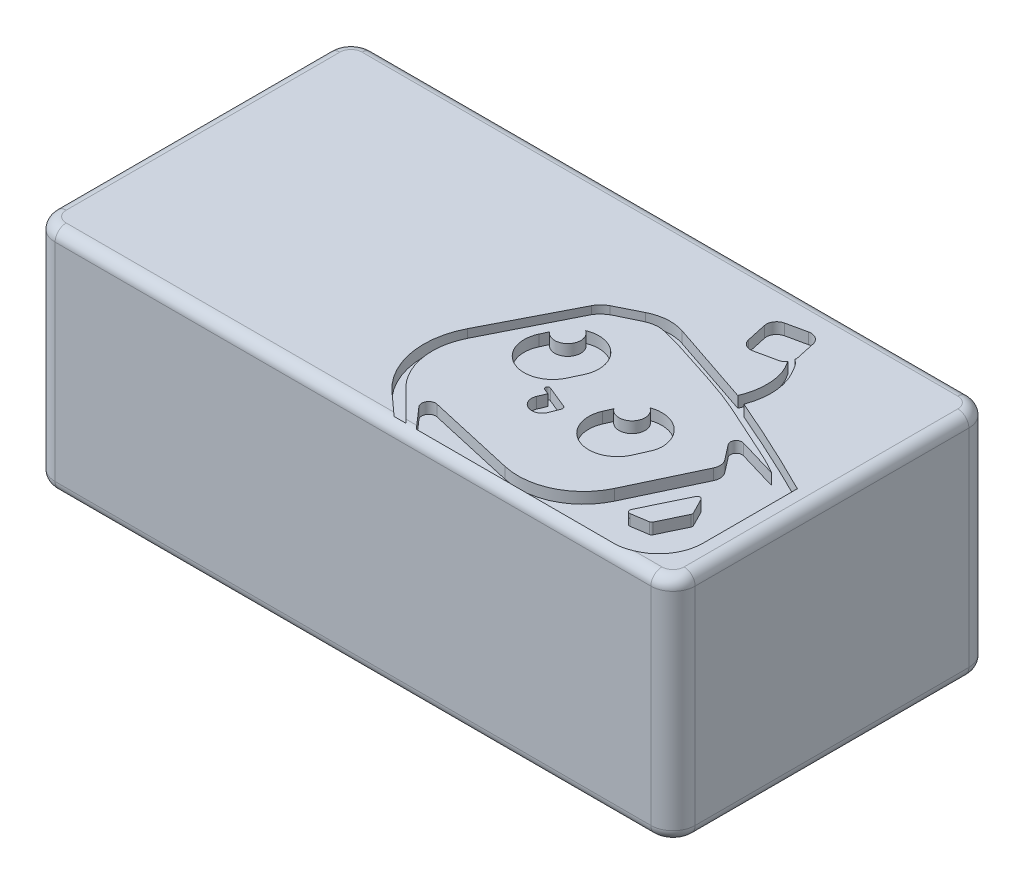
SolidWorks part; units mm, degrees
ref_plane "Front Plane" through (0, 0, 0) normal (0, 0, 1) x (1, 0, 0)
ref_plane "Top Plane" through (0, 0, 0) normal (0, 1, 0) x (1, 0, 0)
ref_plane "Right Plane" through (0, 0, 0) normal (1, 0, 0) x (0, 0, -1)
sketch "Sketch1" plane through (0, 0, 0) normal (0, 1, 0) x (1, 0, 0)
  line L1 (-12.5, -7.5) -> (12.5, -7.5)
  line L2 (-12.5, -7.5) -> (-12.5, 7.5)
  line L3 (-12.5, 7.5) -> (12.5, 7.5)
  line L4 (12.5, -7.5) -> (12.5, 7.5)
  line L5 (-12.5, -7.5) -> (12.5, 7.5) construction
  line L6 (-12.5, 7.5) -> (12.5, -7.5) construction
  point P0 (0, 0)
  dimension "D1" = 15
  dimension "D2" = 25
extrude "Boss-Extrude1" add sketch "Sketch1" along normal mid plane 10.3636
sketch "Sketch2"
  line L0 (180.6347, 501.4527) -> (923.3014, 501.4527) construction
  line L1 (-4.3636, -6.8247) -> (-5.4332, -6.8247)
  line L2 (-7.4332, -4.8247) -> (-7.4332, 4.9107)
  line L3 (-5.4332, 6.9107) -> (5.5194, 6.9107)
  line L4 (7.5194, 4.9107) -> (7.5194, -0.5662)
  line L5 (-4.3636, -6.8247) -> (-5.4332, -5.9231)
  line L6 (-6.1924, -1.7529) -> (-4.2938, 1.9428)
  line L7 (-3.865, 2.3672) -> (-2.7996, 2.901)
  line L8 (-1.2582, 3.0091) -> (2.5252, 1.7368)
  line L9 (1.1191, 3.8213) -> (2.0886, 4.0312)
  line L10 (0.3914, 5.0703) -> (0.5877, 4.1635)
  line L11 (0.7505, 5.6278) -> (1.6384, 5.82)
  line L12 (2.2124, 5.4502) -> (2.4063, 4.5547)
  line L13 (-3.9786, 1.516) -> (-5.8093, -2.1281)
  line L14 (-5.0214, -5.6732) -> (-3.5615, -6.8247)
  line L15 (-3.5615, -6.8247) -> (-3.4302, -6.8247)
  line L16 (-3.4302, -6.8247) -> (-4.2328, -5.907)
  line L17 (-3.9274, -5.3946) -> (0.0559, -6.2971)
  line L18 (3.3761, -4.6797) -> (4.8095, -1.6459)
  line L19 (4.7467, -1.0692) -> (4.2301, -0.4014)
  line L20 (4.5099, 0.0079) -> (6.3202, -0.5264)
  line L21 (5.5264, -3.1622) -> (4.5784, -5.1306)
  line L22 (4.7155, -5.3155) -> (5.4654, -5.1989)
  line L23 (5.5626, -5.1268) -> (6.1187, -3.972)
  line L24 (6.1172, -3.8562) -> (5.7591, -3.1592)
  line L25 (-2.0003, -2.2019) -> (-0.9974, -2.6112)
  line L26 (-2.0746, -2.3822) -> (-1.8339, -2.4825)
  line L27 (-1.8339, -2.4825) -> (-1.9832, -2.8408)
  line L28 (-0.9235, -2.7831) -> (-1.0866, -3.2021)
  line L29 (-4.2134, -0.0245) -> (-4.3655, -0.3473)
  line L30 (-2.0207, -1.4527) -> (-1.7541, -0.8872)
  line L31 (0.2433, -1.578) -> (0.0896, -1.9282)
  line L32 (2.4749, -2.9752) -> (2.7387, -2.3743)
  arc A0 (-5.4332, -6.8247) -> (-7.4332, -4.8247) centre (-5.4332, -4.8247) cw
  arc A1 (5.5194, 6.9107) -> (7.5194, 4.9107) centre (5.5194, 4.9107) cw
  arc A2 (-7.4332, 4.9107) -> (-5.4332, 6.9107) centre (-5.4332, 4.9107) cw
  arc A3 (-5.4332, -5.9231) -> (-6.1924, -1.7529) centre (-3.0963, -3.3434) cw
  arc A4 (-4.2938, 1.9428) -> (-3.865, 2.3672) centre (-3.4302, 1.4991) cw
  arc A5 (-2.7996, 2.901) -> (-1.2582, 3.0091) centre (-1.899, 1.1034) cw
  arc A6 (2.3243, 4.1968) -> (2.0886, 4.0312) centre (2.0103, 4.3931) cw
  arc A7 (1.1191, 3.8213) -> (0.5877, 4.1635) centre (1.0245, 4.2581) cw
  arc A8 (0.3914, 5.0703) -> (0.7505, 5.6278) centre (0.8497, 5.1695) cw
  arc A9 (1.6384, 5.82) -> (2.2124, 5.4502) centre (1.7405, 5.3481) cw
  arc A10 (2.4063, 4.5547) -> (2.4018, 4.4364) centre (2.1731, 4.5042) cw
  arc A11 (3.0047, 1.5345) -> (7.5194, -0.5662) centre (-27.5, -69.926) cw
  arc A12 (-5.0214, -5.6732) -> (-5.8093, -2.1281) centre (-3.2423, -3.4177) cw
  arc A13 (-4.2328, -5.907) -> (-3.9274, -5.3946) centre (-3.9967, -5.7005) cw
  arc A14 (0.0559, -6.2971) -> (3.3761, -4.6797) centre (0.7079, -3.419) ccw
  arc A15 (4.8095, -1.6459) -> (4.7467, -1.0692) centre (4.3077, -1.4088) ccw
  arc A16 (4.2301, -0.4014) -> (4.5099, 0.0079) centre (4.4362, -0.242) cw
  arc A17 (6.1187, -3.972) -> (6.1172, -3.8562) centre (6.0016, -3.9156) ccw
  arc A18 (5.4654, -5.1989) -> (5.5626, -5.1268) centre (5.4454, -5.0704) ccw
  arc A19 (4.5784, -5.1306) -> (4.7155, -5.3155) centre (4.6955, -5.187) ccw
  arc A20 (5.5264, -3.1622) -> (5.7591, -3.1592) centre (5.6435, -3.2186) cw
  arc A21 (-1.9832, -2.8408) -> (-1.0866, -3.2021) centre (-1.537, -3.0267) ccw
  arc A22 (-0.9235, -2.7831) -> (-0.9974, -2.6112) centre (-1.0477, -2.7347) ccw
  arc A23 (-2.0746, -2.3822) -> (-2.0003, -2.2019) centre (-2.0371, -2.2922) cw
  arc A24 (-3.4462, 0.8385) -> (-4.2134, -0.0245) centre (-3.7545, 0.34) cw
  arc A25 (0.2433, -1.578) -> (1.0245, -0.7262) centre (0.7154, -1.2268) ccw
  arc A26 (-3.4462, 0.8385) -> (-1.7259, -0.8201) centre (-2.9478, -0.3661) cw
  arc A27 (1.0245, -0.7262) -> (2.8215, -1.895) centre (1.4807, -1.9907) cw
  arc A28 (-4.3655, -0.3473) -> (-2.0207, -1.4527) centre (-3.1931, -0.9) ccw
  arc A29 (0.0896, -1.9282) -> (2.4749, -2.9752) centre (1.2822, -2.4517) ccw
  arc A30 (-1.7541, -0.8872) -> (-1.7259, -0.8201) centre (-2.5312, -0.5209) ccw
  arc A31 (2.7387, -2.3743) -> (2.8215, -1.895) centre (1.8111, -1.9672) ccw
  spline S0 degree 3 poles (2.5252, 1.7368) (2.6753, 2.0764) (2.7891, 2.6715) (2.6979, 3.5369) (2.4712, 3.981) (2.3243, 4.1968) knots 0 0 0 0 0.430816 0.694599 1 1 1 1
  spline S1 degree 3 poles (2.4018, 4.4364) (2.5923, 4.3118) (2.8046, 3.9742) (3.0654, 3.4498) (3.2578, 2.6374) (3.1673, 1.9694) (3.0047, 1.5345) knots 0 0 0 0 0.211654 0.375148 0.558685 1 1 1 1
  spline S2 degree 3 poles (6.3202, -0.5264) (5.5759, -0.0876) (4.2529, 0.4376) (2.464, 1.3139) (0.9774, 1.7954) (-0.3683, 2.2397) (-1.2804, 2.511) (-1.9161, 2.6531) (-2.3007, 2.5921) (-2.6787, 2.431) (-3.0836, 2.2029) (-3.5846, 2.0136) (-3.8872, 1.717) (-3.9786, 1.516) knots 0 0 0 0 0.229687 0.378724 0.530054 0.645426 0.756187 0.784394 0.817561 0.857699 0.893541 0.941238 1 1 1 1
  dimension "D1" = 2
  dimension "D2" = 0.13
sketch "Sketch4" plane through (0, 5.1818, 0) normal (0, 1, 0) x (1, 0, 0)
  line L0 (-4.3636, -6.8247) -> (-5.4332, -6.8247) construction
  line L1 (-7.4332, -4.8247) -> (-7.4332, 4.9107) construction
  line L2 (7.5194, 4.9107) -> (7.5194, -0.5662) construction
  line L3 (-5.4332, 6.9107) -> (5.5194, 6.9107) construction
  line L4 (-4.3636, -6.8247) -> (-5.4332, -6.8247)
  line L5 (-7.4332, -4.8247) -> (-7.4332, 4.9107)
  line L6 (7.5194, 4.9107) -> (7.5194, -0.5662)
  line L7 (-5.4332, 6.9107) -> (5.5194, 6.9107)
  line L8 (-4.3636, -6.8247) -> (5.5194, -6.8247)
  line L9 (7.5194, -0.5662) -> (7.5194, -4.8247)
  line L10 (-12.5, -7.5) -> (12.5, -7.5) construction
  line L11 (12.5, -7.5) -> (12.5, 7.5) construction
  line L12 (12.5, 7.5) -> (-12.5, 7.5) construction
  line L13 (-12.5, 7.5) -> (-12.5, -7.5) construction
  line L14 (-12.5, -7.5) -> (12.5, -7.5)
  line L15 (12.5, -7.5) -> (12.5, 7.5)
  line L16 (12.5, 7.5) -> (-12.5, 7.5)
  line L17 (-12.5, 7.5) -> (-12.5, -7.5)
  arc A0 (-7.4332, -4.8247) -> (-5.4332, -6.8247) centre (-5.4332, -4.8247) ccw construction
  arc A1 (7.5194, 4.9107) -> (5.5194, 6.9107) centre (5.5194, 4.9107) ccw construction
  arc A2 (-5.4332, 6.9107) -> (-7.4332, 4.9107) centre (-5.4332, 4.9107) ccw construction
  arc A3 (-7.4332, -4.8247) -> (-5.4332, -6.8247) centre (-5.4332, -4.8247) ccw
  arc A4 (7.5194, 4.9107) -> (5.5194, 6.9107) centre (5.5194, 4.9107) ccw
  arc A5 (-5.4332, 6.9107) -> (-7.4332, 4.9107) centre (-5.4332, 4.9107) ccw
  arc A6 (5.5194, -6.8247) -> (7.5194, -4.8247) centre (5.5194, -4.8247) ccw
  dimension "D1" = 2
extrude "Cut-Extrude3" cut sketch "Sketch4" against normal through all
sketch "Sketch5" plane through (0, 5.1818, 0) normal (0, 1, 0) x (1, 0, 0)
  line L0 (-3.9274, -5.3946) -> (0.0559, -6.2971) construction
  line L2 (-3.4302, -6.8247) -> (-4.2328, -5.907) construction
  line L4 (-3.9786, 1.516) -> (-5.8093, -2.1281) construction
  line L5 (4.5099, 0.0079) -> (6.3202, -0.5264) construction
  line L6 (4.7467, -1.0692) -> (4.2301, -0.4014) construction
  line L7 (3.3761, -4.6797) -> (4.8095, -1.6459) construction
  line L8 (-3.9274, -5.3946) -> (0.0559, -6.2971)
  line L10 (-3.4302, -6.8247) -> (-4.2328, -5.907)
  line L12 (-3.9786, 1.516) -> (-5.8093, -2.1281)
  line L13 (4.5099, 0.0079) -> (6.3202, -0.5264)
  line L14 (4.7467, -1.0692) -> (4.2301, -0.4014)
  line L15 (3.3761, -4.6797) -> (4.8095, -1.6459)
  line L16 (2.2124, 5.4502) -> (2.4063, 4.5547) construction
  line L17 (0.7505, 5.6278) -> (1.6384, 5.82) construction
  line L18 (0.3914, 5.0703) -> (0.5877, 4.1635) construction
  line L19 (1.1191, 3.8213) -> (2.0886, 4.0312) construction
  line L20 (2.2124, 5.4502) -> (2.4063, 4.5547)
  line L21 (0.7505, 5.6278) -> (1.6384, 5.82)
  line L22 (0.3914, 5.0703) -> (0.5877, 4.1635)
  line L23 (1.1191, 3.8213) -> (2.0886, 4.0312)
  line L25 (-6.1924, -1.7529) -> (-4.2938, 1.9428) construction
  line L26 (-3.865, 2.3672) -> (-2.7996, 2.901) construction
  line L27 (-1.2582, 3.0091) -> (2.5252, 1.7368) construction
  line L28 (-5.4332, -5.9231) -> (-4.4379, -6.8247)
  line L29 (-6.1924, -1.7529) -> (-4.2938, 1.9428)
  line L30 (-3.865, 2.3672) -> (-2.7996, 2.901)
  line L31 (-1.2582, 3.0091) -> (2.5252, 1.7368)
  line L32 (-4.2134, -0.0245) -> (-4.3655, -0.3473) construction
  line L33 (-2.0207, -1.4527) -> (-1.7541, -0.8872) construction
  line L34 (-4.2134, -0.0245) -> (-4.3655, -0.3473)
  line L35 (-2.0207, -1.4527) -> (-1.7541, -0.8872)
  line L36 (2.4749, -2.9752) -> (2.7387, -2.3743) construction
  line L37 (0.2433, -1.578) -> (0.0896, -1.9282) construction
  line L38 (2.4749, -2.9752) -> (2.7387, -2.3743)
  line L39 (0.2433, -1.578) -> (0.0896, -1.9282)
  line L40 (-0.9235, -2.7831) -> (-1.0866, -3.2021) construction
  line L41 (-1.8339, -2.4825) -> (-1.9832, -2.8408) construction
  line L42 (-2.0746, -2.3822) -> (-1.8339, -2.4825) construction
  line L43 (-2.0003, -2.2019) -> (-0.9974, -2.6112) construction
  line L44 (-0.9235, -2.7831) -> (-1.0866, -3.2021)
  line L45 (-1.8339, -2.4825) -> (-1.9832, -2.8408)
  line L46 (-2.0746, -2.3822) -> (-1.8339, -2.4825)
  line L47 (-2.0003, -2.2019) -> (-0.9974, -2.6112)
  line L48 (-5.272, -5.4587) -> (-3.9061, -6.8247)
  line L49 (-5.4332, -6.8247) -> (5.5194, -6.8247) construction
  line L50 (-4.4379, -6.8247) -> (-3.9061, -6.8247)
  line L51 (-3.4302, -6.8247) -> (5.5194, -6.8247)
  line L52 (7.5194, -0.5662) -> (7.5194, -4.8247)
  line L53 (4.7155, -5.3155) -> (5.4654, -5.1989) construction
  line L54 (5.5626, -5.1268) -> (6.1187, -3.972) construction
  line L55 (6.1172, -3.8562) -> (5.7591, -3.1592) construction
  line L56 (5.5264, -3.1622) -> (4.5784, -5.1306) construction
  line L57 (4.7155, -5.3155) -> (5.4654, -5.1989)
  line L58 (5.5626, -5.1268) -> (6.1187, -3.972)
  line L59 (6.1172, -3.8562) -> (5.7591, -3.1592)
  line L60 (5.5264, -3.1622) -> (4.5784, -5.1306)
  arc A0 (-3.9274, -5.3946) -> (-4.2328, -5.907) centre (-3.9967, -5.7005) ccw construction
  arc A2 (4.5099, 0.0079) -> (4.2301, -0.4014) centre (4.4362, -0.242) ccw construction
  arc A3 (4.8095, -1.6459) -> (4.7467, -1.0692) centre (4.3077, -1.4088) ccw construction
  arc A4 (0.0559, -6.2971) -> (3.3761, -4.6797) centre (0.7079, -3.419) ccw construction
  arc A5 (-3.9274, -5.3946) -> (-4.2328, -5.907) centre (-3.9967, -5.7005) ccw
  arc A7 (4.5099, 0.0079) -> (4.2301, -0.4014) centre (4.4362, -0.242) ccw
  arc A8 (4.8095, -1.6459) -> (4.7467, -1.0692) centre (4.3077, -1.4088) ccw
  arc A9 (0.0559, -6.2971) -> (3.3761, -4.6797) centre (0.7079, -3.419) ccw
  arc A10 (2.4018, 4.4364) -> (2.4063, 4.5547) centre (2.1731, 4.5042) ccw construction
  arc A11 (2.0886, 4.0312) -> (2.3243, 4.1968) centre (2.0103, 4.3931) ccw construction
  arc A12 (2.2124, 5.4502) -> (1.6384, 5.82) centre (1.7405, 5.3481) ccw construction
  arc A13 (0.7505, 5.6278) -> (0.3914, 5.0703) centre (0.8497, 5.1695) ccw construction
  arc A14 (0.5877, 4.1635) -> (1.1191, 3.8213) centre (1.0245, 4.2581) ccw construction
  arc A15 (7.5194, -0.5662) -> (3.0047, 1.5345) centre (-27.5, -69.926) ccw construction
  arc A16 (2.4018, 4.4364) -> (2.4063, 4.5547) centre (2.1731, 4.5042) ccw
  arc A17 (2.0886, 4.0312) -> (2.3243, 4.1968) centre (2.0103, 4.3931) ccw
  arc A18 (2.2124, 5.4502) -> (1.6384, 5.82) centre (1.7405, 5.3481) ccw
  arc A19 (0.7505, 5.6278) -> (0.3914, 5.0703) centre (0.8497, 5.1695) ccw
  arc A20 (0.5877, 4.1635) -> (1.1191, 3.8213) centre (1.0245, 4.2581) ccw
  arc A21 (7.5194, -0.5662) -> (3.0047, 1.5345) centre (-27.5, -69.926) ccw
  arc A22 (-6.1924, -1.7529) -> (-5.4332, -5.9231) centre (-3.0963, -3.3434) ccw construction
  arc A23 (-3.865, 2.3672) -> (-4.2938, 1.9428) centre (-3.4302, 1.4991) ccw construction
  arc A24 (-1.2582, 3.0091) -> (-2.7996, 2.901) centre (-1.899, 1.1034) ccw construction
  arc A25 (-6.1924, -1.7529) -> (-5.4332, -5.9231) centre (-3.0963, -3.3434) ccw
  arc A26 (-3.865, 2.3672) -> (-4.2938, 1.9428) centre (-3.4302, 1.4991) ccw
  arc A27 (-1.2582, 3.0091) -> (-2.7996, 2.901) centre (-1.899, 1.1034) ccw
  arc A28 (-4.3655, -0.3473) -> (-2.0207, -1.4527) centre (-3.1931, -0.9) ccw construction
  arc A29 (-1.7541, -0.8872) -> (-1.7259, -0.8201) centre (-2.5312, -0.5209) ccw construction
  arc A30 (-1.7259, -0.8201) -> (-3.4462, 0.8385) centre (-2.9478, -0.3661) ccw construction
  arc A31 (-4.2134, -0.0245) -> (-3.4462, 0.8385) centre (-3.7545, 0.34) ccw construction
  arc A32 (-4.3655, -0.3473) -> (-2.0207, -1.4527) centre (-3.1931, -0.9) ccw
  arc A33 (-1.7541, -0.8872) -> (-1.7259, -0.8201) centre (-2.5312, -0.5209) ccw
  arc A34 (-1.7259, -0.8201) -> (-3.4462, 0.8385) centre (-2.9478, -0.3661) ccw
  arc A35 (-4.2134, -0.0245) -> (-3.4462, 0.8385) centre (-3.7545, 0.34) ccw
  arc A36 (2.8215, -1.895) -> (1.0245, -0.7262) centre (1.4807, -1.9907) ccw construction
  arc A37 (2.7387, -2.3743) -> (2.8215, -1.895) centre (1.8111, -1.9672) ccw construction
  arc A38 (0.0896, -1.9282) -> (2.4749, -2.9752) centre (1.2822, -2.4517) ccw construction
  arc A39 (0.2433, -1.578) -> (1.0245, -0.7262) centre (0.7154, -1.2268) ccw construction
  arc A40 (2.8215, -1.895) -> (1.0245, -0.7262) centre (1.4807, -1.9907) ccw
  arc A41 (2.7387, -2.3743) -> (2.8215, -1.895) centre (1.8111, -1.9672) ccw
  arc A42 (0.0896, -1.9282) -> (2.4749, -2.9752) centre (1.2822, -2.4517) ccw
  arc A43 (0.2433, -1.578) -> (1.0245, -0.7262) centre (0.7154, -1.2268) ccw
  arc A44 (-0.9235, -2.7831) -> (-0.9974, -2.6112) centre (-1.0477, -2.7347) ccw construction
  arc A45 (-1.9832, -2.8408) -> (-1.0866, -3.2021) centre (-1.537, -3.0267) ccw construction
  arc A46 (-2.0003, -2.2019) -> (-2.0746, -2.3822) centre (-2.0371, -2.2922) ccw construction
  arc A47 (-0.9235, -2.7831) -> (-0.9974, -2.6112) centre (-1.0477, -2.7347) ccw
  arc A48 (-1.9832, -2.8408) -> (-1.0866, -3.2021) centre (-1.537, -3.0267) ccw
  arc A49 (-2.0003, -2.2019) -> (-2.0746, -2.3822) centre (-2.0371, -2.2922) ccw
  arc A50 (-5.8093, -2.1281) -> (-5.272, -5.4587) centre (-3.2348, -3.4214) ccw
  arc A51 (5.5194, -6.8247) -> (7.5194, -4.8247) centre (5.5194, -4.8247) ccw construction
  arc A52 (5.5194, -6.8247) -> (7.5194, -4.8247) centre (5.5194, -4.8247) ccw
  arc A53 (4.5784, -5.1306) -> (4.7155, -5.3155) centre (4.6955, -5.187) ccw construction
  arc A54 (5.4654, -5.1989) -> (5.5626, -5.1268) centre (5.4454, -5.0704) ccw construction
  arc A55 (6.1187, -3.972) -> (6.1172, -3.8562) centre (6.0016, -3.9156) ccw construction
  arc A56 (5.7591, -3.1592) -> (5.5264, -3.1622) centre (5.6435, -3.2186) ccw construction
  arc A57 (4.5784, -5.1306) -> (4.7155, -5.3155) centre (4.6955, -5.187) ccw
  arc A58 (5.4654, -5.1989) -> (5.5626, -5.1268) centre (5.4454, -5.0704) ccw
  arc A59 (6.1187, -3.972) -> (6.1172, -3.8562) centre (6.0016, -3.9156) ccw
  arc A60 (5.7591, -3.1592) -> (5.5264, -3.1622) centre (5.6435, -3.2186) ccw
  spline S0 degree 3 poles (-1220.2203, -2737.8202) (56.1541, 7.2457) (23.6794, -9.078) (2.464, 1.3139) (0.9774, 1.7954) (-0.3683, 2.2397) (-1.2804, 2.511) (-1.9161, 2.6531) (-2.3007, 2.5921) (-2.6787, 2.431) (-3.0836, 2.2029) (-11.2083, -0.8674) (13.6668, -74.4286) (2977.7963, 321.0421) knots -5.756169 -5.756169 -5.756169 -5.756169 0.229687 0.378724 0.530054 0.645426 0.756187 0.784394 0.817561 0.857699 0.893541 0.941238 3.165317 3.165317 3.165317 3.165317 only from (6.3202, -0.5264) to (-3.9786, 1.516) construction
  spline S1 degree 3 poles (6.3202, -0.5264) (5.5759, -0.0876) (4.2529, 0.4376) (2.464, 1.3139) (0.9774, 1.7954) (-0.3683, 2.2397) (-1.2804, 2.511) (-1.9161, 2.6531) (-2.3007, 2.5921) (-2.6787, 2.431) (-3.0836, 2.2029) (-3.5846, 2.0136) (-3.8872, 1.717) (-3.9786, 1.516) knots 0 0 0 0 0.229687 0.378724 0.530054 0.645426 0.756187 0.784394 0.817561 0.857699 0.893541 0.941238 1 1 1 1
  spline S2 degree 3 poles (-1510.1189, 2588.8055) (-140.8528, -26.393) (4.553, -14.0506) (1.3265, 16.5383) (-131.2193, -6.3568) (2772.9681, -1144.5673) knots -19.323242 -19.323242 -19.323242 -19.323242 0.430816 0.694599 16.023711 16.023711 16.023711 16.023711 only from (2.5252, 1.7368) to (2.3243, 4.1968) construction
  spline S3 degree 3 poles (-2101.6125, -2133.8082) (-16.8857, 11.7611) (-0.3267, 10.27) (3.0654, 3.4498) (7.3957, -14.8347) (-180.6056, -51.9895) (819.0825, 2884.3539) knots -6.708046 -6.708046 -6.708046 -6.708046 0.211654 0.375148 0.558685 17.954231 17.954231 17.954231 17.954231 only from (2.4018, 4.4364) to (3.0047, 1.5345) construction
  spline S4 degree 3 poles (2.5252, 1.7368) (2.6753, 2.0764) (2.7891, 2.6715) (2.6979, 3.5369) (2.4712, 3.981) (2.3243, 4.1968) knots 0 0 0 0 0.430816 0.694599 1 1 1 1
  spline S5 degree 3 poles (2.4018, 4.4364) (2.5923, 4.3118) (2.8046, 3.9742) (3.0654, 3.4498) (3.2578, 2.6374) (3.1673, 1.9694) (3.0047, 1.5345) knots 0 0 0 0 0.211654 0.375148 0.558685 1 1 1 1
  point P81 (6.1172, -3.8562)
extrude "Cut-Extrude4" cut sketch "Sketch5" against normal blind 0.5
sketch "Sketch9" plane through (0, 5.1818, 0) normal (0, 1, 0) x (1, 0, 0)
  line L0 (-20.3897, 0) -> (0, 0) construction
  line L1 (8.5194, 7.1818) -> (-20.3897, 7.1818)
  line L2 (8.5194, 7.1818) -> (8.5194, -7.1818)
  line L3 (8.5194, -7.1818) -> (-20.3897, -7.1818)
  line L4 (-20.3897, 7.1818) -> (-20.3897, -7.1818)
  line L11 (5.5194, 6.9107) -> (-5.4332, 6.9107) construction
  line L12 (5.5194, 6.9107) -> (-5.4332, 6.9107)
  line L13 (-7.4332, 4.9107) -> (-7.4332, -4.8247) construction
  line L14 (-7.4332, 4.9107) -> (-7.4332, -4.8247)
  line L15 (7.5194, -4.8247) -> (7.5194, -0.5662) construction
  line L16 (7.5194, -0.5662) -> (7.5194, 4.9107) construction
  line L17 (7.5194, -4.8247) -> (7.5194, -0.5662)
  line L18 (7.5194, -0.5662) -> (7.5194, 4.9107)
  line L19 (-5.4332, -6.8247) -> (5.5194, -6.8247)
  arc A11 (-5.4332, 6.9107) -> (-7.4332, 4.9107) centre (-5.4332, 4.9107) ccw construction
  arc A12 (-5.4332, 6.9107) -> (-7.4332, 4.9107) centre (-5.4332, 4.9107) ccw
  arc A13 (-7.4332, -4.8247) -> (-5.4332, -6.8247) centre (-5.4332, -4.8247) ccw construction
  arc A14 (-7.4332, -4.8247) -> (-5.4332, -6.8247) centre (-5.4332, -4.8247) ccw
  arc A15 (7.5194, 4.9107) -> (5.5194, 6.9107) centre (5.5194, 4.9107) ccw construction
  arc A16 (7.5194, 4.9107) -> (5.5194, 6.9107) centre (5.5194, 4.9107) ccw
  arc A17 (5.5194, -6.8247) -> (7.5194, -4.8247) centre (5.5194, -4.8247) ccw construction
  arc A18 (5.5194, -6.8247) -> (7.5194, -4.8247) centre (5.5194, -4.8247) ccw
  dimension "D1" = 14.3636
  dimension "D2" = 28.9091
  dimension "D3" = 1
extrude "Boss-Extrude2" add sketch "Sketch9" against normal up to surface (10.3636 mm away) up to face at (0.0431, -5.1818, -0.043)
fillet "Fillet3" radius 1 4 edges at (-20.3897, 0, -7.1818) (8.5194, 0, -7.1818) (8.5194, 0, 7.1818) (-20.3897, 0, 7.1818)
fillet "Fillet2" radius 0.5 16 edges at (8.5194, 5.1818, 0) (8.5194, -5.1818, 0) (-20.0968, -5.1818, -6.8889) (-5.9352, -5.1818, -7.1818) (8.2265, -5.1818, -6.8889) (8.2265, -5.1818, 6.8889) (-5.9352, -5.1818, 7.1818) (-20.0968, -5.1818, 6.8889) (-20.0968, 5.1818, -6.8889) (-5.9352, 5.1818, -7.1818) (8.2265, 5.1818, -6.8889) (8.2265, 5.1818, 6.8889) (-5.9352, 5.1818, 7.1818) (-20.0968, 5.1818, 6.8889) (-20.3897, -5.1818, 0) (-20.3897, 5.1818, 0)
mirror "Mirror1" about plane through (0, 0, 0) normal (0, 1, 0) of "Cut-Extrude4"
scale "Scale1" scale about centroid uniform scaling yes scale factor 1.1
